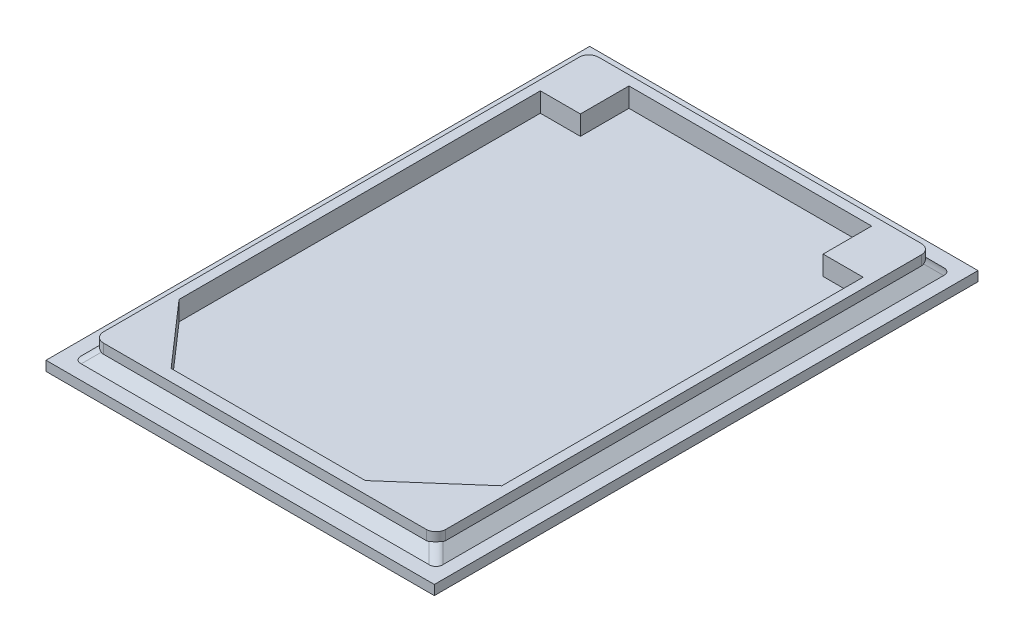
SolidWorks part; units mm, degrees
ref_plane "Спереди" through (0, 0, 0) normal (0, 0, 1) x (1, 0, 0)
ref_plane "Сверху" through (0, 0, 0) normal (0, 1, 0) x (1, 0, 0)
ref_plane "Справа" through (0, 0, 0) normal (1, 0, 0) x (0, 0, -1)
sketch "Эскиз1" plane through (0, 0, 0) normal (0, 1, 0) x (1, 0, 0)
  line L1 (-15.039, 14.7021) -> (24.961, 14.7021)
  line L2 (-15.039, 14.7021) -> (-15.039, -41.2979)
  line L3 (-15.039, -41.2979) -> (24.961, -41.2979)
  line L4 (24.961, 14.7021) -> (24.961, -41.2979)
  dimension "D1" = 40
  dimension "D2" = 56
extrude "Бобышка-Вытянуть1" add sketch "Эскиз1" along normal blind 1
sketch "Эскиз2" plane through (0, 1, 0) normal (0, 1, 0) x (1, 0, 0)
  line L0 (-7.4866, 11.1952) -> (17.5134, 11.1952)
  line L1 (-12.6116, 12.1952) -> (22.6384, 12.1952)
  line L2 (-12.6116, 12.1952) -> (-12.6116, -38.8048)
  line L3 (-12.6116, -38.8048) -> (22.6384, -38.8048)
  line L4 (22.6384, 12.1952) -> (22.6384, -38.8048)
  line L5 (17.5134, 11.1952) -> (17.5134, 6.1952)
  line L6 (17.5134, 6.1952) -> (21.6384, 6.1952)
  line L7 (21.6384, 6.1952) -> (21.6384, -31.0198)
  line L8 (21.6384, -31.0198) -> (14.1384, -37.5867)
  line L9 (14.1384, -37.5867) -> (-5.8616, -37.5867)
  line L10 (-5.8616, -37.5867) -> (-11.6116, -31.0198)
  line L11 (-11.6116, -31.0198) -> (-11.6116, 6.1952)
  line L12 (-11.6116, 6.1952) -> (-7.4866, 6.1952)
  line L13 (-7.4866, 6.1952) -> (-7.4866, 11.1952)
  dimension "D1" = 35.25
  dimension "D2" = 51
  dimension "D3" = 25
  dimension "D4" = 5
  dimension "D5" = 5
  dimension "D6" = 37.215
  dimension "D7" = 37.215
  dimension "D8" = 4.125
  dimension "D9" = 4.125
  dimension "D10" = 20
  dimension "D12" = 7.5
  dimension "D11" = 5.75
  dimension "D13" = 1
  dimension "D14" = 1
  dimension "D15" = 1
extrude "Бобышка-Вытянуть2" add sketch "Эскиз2" along normal blind 2
chamfer "Фаска1" distance 1 angle 45 4 edges at (-12.6116, 1, 13.3048) (5.0134, 1, -12.1952) (22.6384, 1, 13.3048) (5.0134, 1, 38.8048)
fillet "Скругление1" radius 1 8 edges at (-13.1116, 1.5, -12.6952) (-12.6116, 2.5, -12.1952) (23.1384, 1.5, -12.6952) (22.6384, 2.5, -12.1952) (23.1384, 1.5, 39.3048) (22.6384, 2.5, 38.8048) (-13.1116, 1.5, 39.3048) (-12.6116, 2.5, 38.8048)
equation "\"D5@Эскиз2\"=\"D4@Эскиз2\""
equation "\"D7@Эскиз2\"=\"D6@Эскиз2\""
equation "\"D9@Эскиз2\"=\"D8@Эскиз2\""
